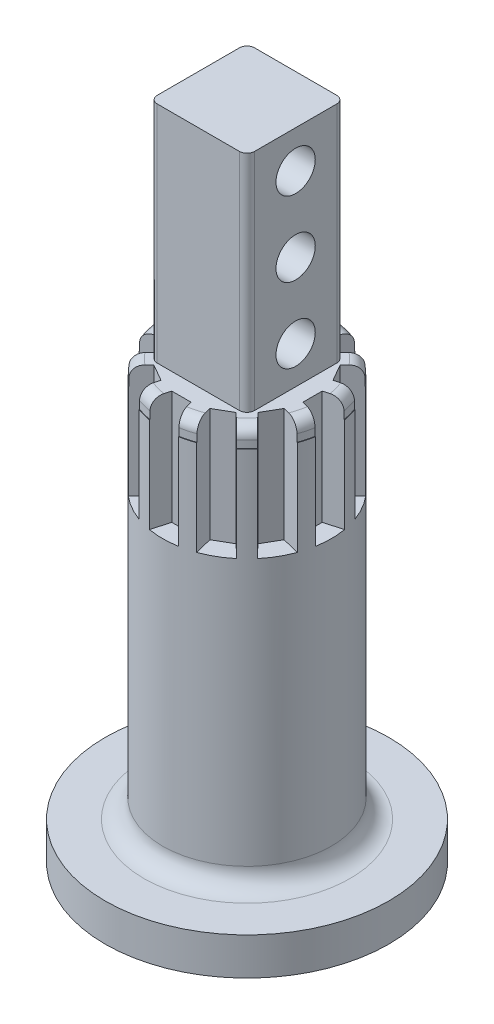
SolidWorks part; units mm, degrees
ref_plane "Front Plane" through (0, 0, 0) normal (0, 0, 1) x (1, 0, 0)
ref_plane "Top Plane" through (0, 0, 0) normal (0, 1, 0) x (1, 0, 0)
ref_plane "Right Plane" through (0, 0, 0) normal (1, 0, 0) x (0, 0, -1)
sketch "Sketch1" plane through (0, 0, 0) normal (0, 1, 0) x (1, 0, 0)
  circle A0 centre (0, 0) radius 37.9
extrude "Boss-Extrude1" add sketch "Sketch1" along normal blind 10
sketch "Sketch2" plane through (0, 10, 0) normal (0, 1, 0) x (1, 0, 0)
  circle A0 centre (0, 0) radius 22.53
extrude "Boss-Extrude2" add sketch "Sketch2" along normal blind 101.6
fillet "Fillet1" radius 5 1 edges at (0, 10, 22.53)
sketch "Sketch8" plane through (0, 111.6, 0) normal (0, 1, 0) x (1, 0, 0)
  line L0 (0, 22.53) -> (-4, 22.53)
  line L1 (0, 22.53) -> (4, 22.53)
  line L8 (-2.5662, 17.53) -> (2.5662, 17.53)
  line L9 (2.5662, 17.53) -> (4, 22.53)
  line L10 (-2.5662, 17.53) -> (-4, 22.53)
  circle A1 centre (0, 0) radius 22.53 construction
  dimension "D1" = 4
  dimension "D2" = 5
  dimension "D3" = 4
extrude "Cut-Extrude3" cut sketch "Sketch8" against normal blind 25.4 and the other way blind 5
pattern_circular "CirPattern1" count 12 over 360 about axis through (0, 111.6, 0) along (0, 1, 0) of "Cut-Extrude3"
sketch "Sketch5" plane through (0, 111.6, 0) normal (0, 1, 0) x (1, 0, 0)
  circle A0 centre (0, 0) radius 22.4
extrude "Boss-Extrude3" add sketch "Sketch5" along normal blind 5
sketch "Sketch6" plane through (0, 116.6, 0) normal (0, 1, 0) x (1, 0, 0)
  line L0 (0, 0) -> (13, 0)
  line L1 (0, 0) -> (-13, 0)
  line L2 (-13, 0) -> (-13, 13)
  line L3 (-13, 0) -> (-13, -13)
  line L4 (-13, 13) -> (13, 13)
  line L5 (13, 13) -> (13, -13)
  line L6 (13, -13) -> (-13, -13)
  dimension "D1" = 13
  dimension "D2" = 13
  dimension "D3" = 13
  dimension "D4" = 13
extrude "Boss-Extrude4" add sketch "Sketch6" along normal blind 60 contours L5 L4 L2 L1 L0 | L6 L5 L0 L1 L3 region at (0, 116.6, -6.5) region at (0, 116.6, 6.5)
sketch "Sketch7" plane through (13, 0, 0) normal (1, 0, 0) x (0, 0, -1)
  line L7 (0, 176.6) -> (0, 116.6)
  line L9 (13, 176.6) -> (-13, 176.6) construction
  line L10 (22.4, 116.6) -> (-22.4, 116.6) construction
  line L11 (13, 116.6) -> (-13, 116.6) construction
  circle A6 centre (0, 146.6) radius 5.25
  circle A7 centre (0, 166.6) radius 5.25
  circle A8 centre (0, 126.6) radius 5.25
  dimension "D2" = 10
  dimension "D1" = 10
extrude "Cut-Extrude2" cut sketch "Sketch7" against normal blind 46 contours L7 A7 | L7 A7 | L7 A6 | L7 A6 | L7 A8 | L7 A8 region at (13, 166.6, -2.2282) region at (13, 126.6, -2.2282) region at (13, 126.6, 2.2282) region at (13, 146.6, -2.2282) region at (13, 146.6, 2.2282) region at (13, 166.6, 2.2282)
extrude "Cut-Extrude4" cut sketch "Sketch8<2>" along normal blind 25.4
sketch "Sketch8<2>" plane through (0, 111.6, 0) normal (0, 1, 0) x (1, 0, 0) same geometry as "Sketch8"
pattern_circular "CirPattern2" count 12 over 360 about axis through (0, 116.6, 0) along (0, 1, 0) of "Cut-Extrude4"
fillet "Fillet3" radius 3 12 edges at (-5.7975, 116.6, -21.6367) (-21.6367, 116.6, -5.7975) (-21.6367, 116.6, 5.7975) (-15.8392, 116.6, 15.8392) (-5.7975, 116.6, 21.6367) (5.7975, 116.6, 21.6367) (15.8392, 116.6, 15.8392) (21.6367, 116.6, 5.7975) (21.6367, 116.6, -5.7975) (15.8392, 116.6, -15.8392) (5.7975, 116.6, -21.6367) (-15.8392, 116.6, -15.8392)
fillet "Fillet4" radius 2 4 edges at (-13, 146.6, -13) (13, 146.6, -13) (13, 146.6, 13) (-13, 146.6, 13)
